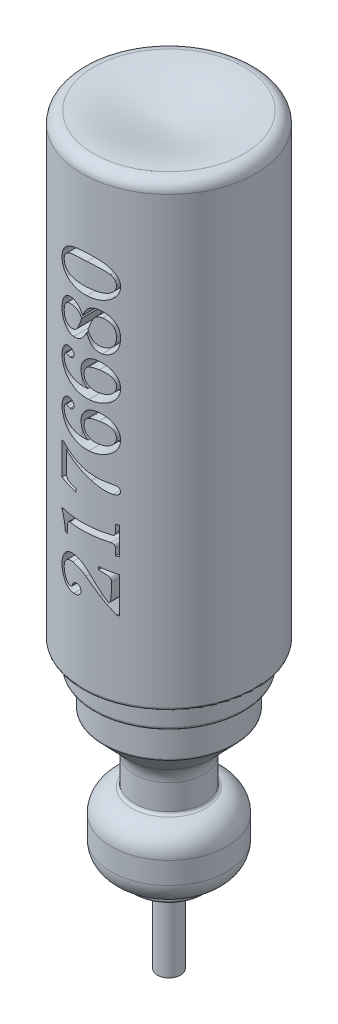
SolidWorks part; units mm, degrees
ref_plane "Front Plane" through (0, 0, 0) normal (0, 0, 1) x (1, 0, 0)
ref_plane "Top Plane" through (0, 0, 0) normal (0, 1, 0) x (1, 0, 0)
ref_plane "Right Plane" through (0, 0, 0) normal (1, 0, 0) x (0, 0, -1)
sketch "Sketch1" plane through (0, 0, 0) normal (0, 0, 1) x (1, 0, 0)
  line L0 (0, 0) -> (0, -252) construction
  line L1 (-15, -2) -> (-15, -78.95)
  line L2 (-14.5, -79.45) -> (-13.5, -79.45)
  line L3 (-13, -79.95) -> (-13, -83.2485)
  line L4 (-12.5, -83.7485) -> (-11.8381, -83.7485)
  line L5 (-11.3381, -84.2485) -> (-11.3381, -89.2008)
  line L6 (-11.3042, -89.3816) -> (-7.1258, -93.6985)
  line L7 (-6, -96.4804) -> (-6, -100.813)
  line L8 (-4, -114.5531) -> (-5.7, -114.5531)
  line L9 (-10, -105.2851) -> (-10, -109.0572)
  line L10 (-6, -114.2531) -> (-6, -113.3467)
  line L11 (-2, -128.5531) -> (0, -128.5531)
  line L12 (0, -2) -> (0, -128.5531)
  line L13 (-2, -116.5531) -> (-2, -128.5531)
  arc A0 (-15, -2) -> (-13, 0) centre (-13, -2) cw
  arc A1 (-10, -105.2851) -> (-6.4444, -101.3099) centre (-6, -105.2851) cw
  arc A2 (-10, -109.0572) -> (-6.2791, -113.0475) centre (-6, -109.0572) ccw
  arc A3 (-7.1258, -93.6985) -> (-6, -96.4804) centre (-10, -96.4804) cw
  arc A4 (-5.7, -114.5531) -> (-6, -114.2531) centre (-5.7, -114.2531) cw
  arc A5 (-6, -113.3467) -> (-6.2791, -113.0475) centre (-6.3, -113.3467) ccw
  arc A6 (-2, -116.5531) -> (-4, -114.5531) centre (-4, -116.5531) ccw
  arc A7 (-11.3381, -89.2008) -> (-11.3042, -89.3816) centre (-10.8381, -89.2008) ccw
  arc A8 (-11.8381, -83.7485) -> (-11.3381, -84.2485) centre (-11.8381, -84.2485) cw
  arc A9 (-13, -83.2485) -> (-12.5, -83.7485) centre (-12.5, -83.2485) ccw
  arc A10 (-13.5, -79.45) -> (-13, -79.95) centre (-13.5, -79.95) cw
  arc A11 (-15, -78.95) -> (-14.5, -79.45) centre (-14.5, -78.95) ccw
  arc A12 (-6, -100.813) -> (-6.4444, -101.3099) centre (-6.5, -100.813) cw
  spline S0 degree 3 poles (-13, 0) (-8.6157, 0) (-5.4759, -1.5914) (0, -2) knots 0 0 0 0 1 1 1 1
  point P22 (-10, -98.9189)
  point P25 (-10, -108.9189)
  point P44 (-15, -79.45)
  point P47 (-2, -114)
  point P50 (-2, -126)
  dimension "D2" = 15
  dimension "D1" = 2
  dimension "D8" = 4
  dimension "D9" = 4
  dimension "D10" = 4
  dimension "D11" = 0.3
  dimension "D14" = 2
  dimension "D5" = 0.5
  dimension "D3" = 12
  dimension "D6" = 77.45
  dimension "D7" = 10
revolve "Revolve1" add sketch "Sketch1" angle 360 about L0
ref_plane "Plane1" through (0, -128.5531, 0) normal (0, -1, 0) x (-1, 0, 0)
sketch "Sketch2" plane through (0, -128.5531, 0) normal (0, -1, 0) x (-1, 0, 0)
  circle A0 centre (0, 0) radius 1.5
  dimension "D1" = 3
extrude "Cut-Extrude1" cut sketch "Sketch2" against normal blind 12
ref_plane "Plane2" through (0, 0, 28.0845) normal (0, 0, 1) x (1, 0, 0)
sketch "Sketch3" plane through (0, 0, 28.0845) normal (0, 0, 1) x (1, 0, 0)
  line L0 (5.4366, -66.6749) -> (5.4366, -12.6838) construction
  text T0 "2176680" font "Century Schoolbook" height 10
extrude "Cut-Extrude2" cut sketch "Sketch3" against normal blind 17
